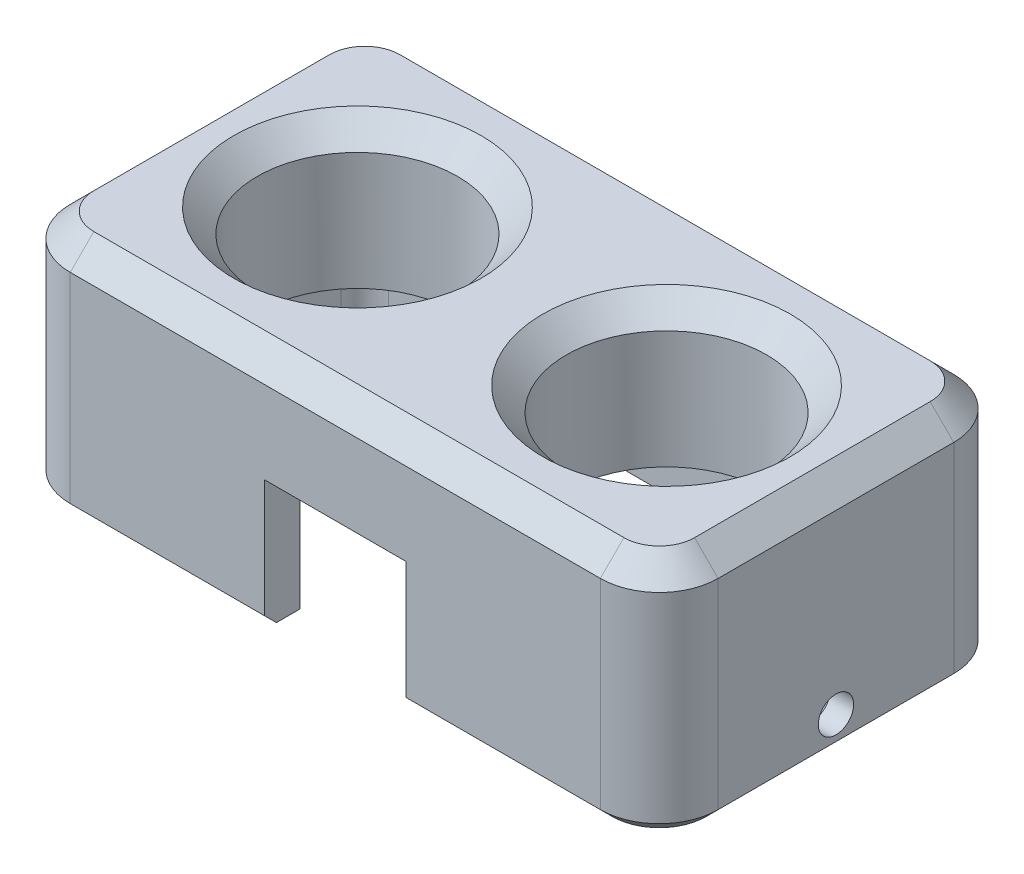
SolidWorks part; units mm, degrees
ref_plane "Front Plane" through (0, 0, 0) normal (0, 0, 1) x (1, 0, 0)
ref_plane "Top Plane" through (0, 0, 0) normal (0, 1, 0) x (1, 0, 0)
ref_plane "Right Plane" through (0, 0, 0) normal (1, 0, 0) x (0, 0, -1)
sketch "Sketch1" plane through (0, 0, 0) normal (0, 1, 0) x (1, 0, 0)
  line L1 (-27.5, -15) -> (27.5, -15)
  line L2 (-27.5, -15) -> (-27.5, 15)
  line L3 (-27.5, 15) -> (27.5, 15)
  line L4 (27.5, -15) -> (27.5, 15)
  line L5 (-27.5, -15) -> (27.5, 15) construction
  line L6 (-27.5, 15) -> (27.5, -15) construction
  point P0 (0, 0)
  dimension "D1" = 30
  dimension "D2" = 55
extrude "Boss-Extrude1" add sketch "Sketch1" along normal blind 12
sketch "Sketch2" plane through (0, 12, 0) normal (0, 1, 0) x (1, 0, 0)
  line L0 (0, 3.5755) -> (0, -2.1377) construction
  line L1 (0, 0) -> (-13.12, 0) construction
  circle A0 centre (-13.12, 0) radius 8.5
  circle A1 centre (13.12, 0) radius 8.5
  circle A2 centre (-13.12, 0) radius 10.5
  circle A3 centre (13.12, 0) radius 10.5
  dimension "D1" = 17
  dimension "D3" = 2
  dimension "D2" = 26.24
extrude "Cut-Extrude1" cut sketch "Sketch2" against normal through all contours A0 | A1 region at (-13.12, 12, 0) region at (13.12, 12, 0)
sketch "Sketch4" plane through (0, 0, 0) normal (0, -1, 0) x (1, 0, 0)
  line L0 (0, -15) -> (0, -7.5) construction
  line L2 (27.5, -15) -> (-27.5, -15) construction
  line L3 (6, -10) -> (-6, -10)
  line L4 (6, -10) -> (6, -5)
  line L5 (6, -5) -> (-6, -5)
  line L6 (-6, -10) -> (-6, -5)
  line L7 (6, -10) -> (-6, -5) construction
  line L8 (6, -5) -> (-6, -10) construction
  dimension "D1" = 12
  dimension "D2" = 5
  dimension "D3" = 5
extrude "Cut-Extrude2" [suppressed] cut sketch "Sketch4" against normal blind 5
fillet "Fillet1" [suppressed] radius 2
sketch "Sketch5" plane through (0, 0, 0) normal (0, -1, 0) x (1, 0, 0)
  line L0 (-27.5, 15) -> (27.5, 15) construction
  line L1 (-6, 6) -> (6, 6)
  line L2 (-6, 6) -> (-6, 15)
  line L3 (-6, 15) -> (6, 15)
  line L4 (6, 6) -> (6, 15)
  line L5 (-6, 6) -> (6, 15) construction
  line L6 (-6, 15) -> (6, 6) construction
  line L7 (0, 10.5) -> (0, 15) construction
  point P0 (0, 10.5)
  dimension "D1" = 12
  dimension "D2" = 9
extrude "Cut-Extrude3" cut sketch "Sketch5" against normal blind 3
fillet "Fillet2" radius 5 4 edges at (27.5, 6, 15) (-27.5, 6, -15) (27.5, 6, -15) (-27.5, 6, 15)
sketch "Sketch6" plane through (0, 0, 0) normal (0, -1, 0) x (1, 0, 0)
  line L8 (24.5, -10) -> (24.5, 10)
  line L9 (22.5, 12) -> (9, 12)
  line L13 (-9, 12) -> (-22.5, 12)
  line L14 (-24.5, 10) -> (-24.5, -10)
  line L15 (-22.5, -12) -> (22.5, -12)
  line L16 (27.5, -10) -> (27.5, 10)
  line L17 (22.5, 15) -> (6, 15)
  line L18 (6, 15) -> (6, 6)
  line L19 (6, 6) -> (-6, 6)
  line L20 (-6, 6) -> (-6, 15)
  line L21 (-6, 15) -> (-22.5, 15)
  line L22 (-27.5, 10) -> (-27.5, -10)
  line L23 (-22.5, -15) -> (22.5, -15)
  line L24 (27.5, -10) -> (27.5, 10)
  line L25 (22.5, 15) -> (6, 15)
  line L26 (6, 15) -> (6, 6)
  line L27 (6, 6) -> (-6, 6)
  line L28 (-6, 6) -> (-6, 15)
  line L29 (-6, 15) -> (-22.5, 15)
  line L30 (-27.5, 10) -> (-27.5, -10)
  line L31 (-22.5, -15) -> (22.5, -15)
  line L32 (-9, 3) -> (-9, 12) construction
  line L33 (9, 3) -> (-9, 3) construction
  line L34 (9, 12) -> (9, 3) construction
  line L35 (-9, 12) -> (-6, 12)
  line L36 (0, 16.6951) -> (0, 15.068) construction
  line L37 (9, 12) -> (6, 12)
  arc A4 (24.5, 10) -> (22.5, 12) centre (22.5, 10) ccw
  arc A5 (-22.5, 12) -> (-24.5, 10) centre (-22.5, 10) ccw
  arc A6 (-24.5, -10) -> (-22.5, -12) centre (-22.5, -10) ccw
  arc A7 (22.5, -12) -> (24.5, -10) centre (22.5, -10) ccw
  arc A8 (27.5, 10) -> (22.5, 15) centre (22.5, 10) ccw
  arc A9 (-22.5, 15) -> (-27.5, 10) centre (-22.5, 10) ccw
  arc A10 (-27.5, -10) -> (-22.5, -15) centre (-22.5, -10) ccw
  arc A11 (22.5, -15) -> (27.5, -10) centre (22.5, -10) ccw
  arc A12 (27.5, 10) -> (22.5, 15) centre (22.5, 10) ccw
  arc A13 (-22.5, 15) -> (-27.5, 10) centre (-22.5, 10) ccw
  arc A14 (-27.5, -10) -> (-22.5, -15) centre (-22.5, -10) ccw
  arc A15 (22.5, -15) -> (27.5, -10) centre (22.5, -10) ccw
  line M15 (27.5, -10) -> (27.5, 10)
  arc M16 (27.5, 10) -> (22.5, 15) centre (22.5, 10) ccw
  line M17 (22.5, 15) -> (6, 15)
  line M18 (6, 15) -> (6, 6)
  line M21 (-6, 15) -> (-22.5, 15)
  arc M22 (-22.5, 15) -> (-27.5, 10) centre (-22.5, 10) ccw
  line M23 (-27.5, 10) -> (-27.5, -10)
  arc M24 (-27.5, -10) -> (-22.5, -15) centre (-22.5, -10) ccw
  line M25 (-22.5, -15) -> (22.5, -15)
  arc M26 (22.5, -15) -> (27.5, -10) centre (22.5, -10) ccw
  dimension "D1" = 0
  dimension "D2" = 3
extrude "Boss-Extrude3" add sketch "Sketch6" along normal blind 8 contours A7 L15 A6 L14 A5 L13 L35 L28 L37 L9 A4 L8 M21 M22 M23 M24 M25 M26 M15 M16 M17 M18 region at (25.1265, 0, 0)
hole_wizard "Ø3.0mm Dowel Hole1" positions "Sketch7" profile "Sketch9" hole size "Ø3.0" standard "ANSI Metric" end condition through all
sketch "Sketch7" plane through (-27.5, 0, 0) normal (-1, 0, 0) x (0, 0, 1)
  line L0 (0, -8) -> (0, -5) construction
  line L2 (10, -8) -> (-10, -8) construction
  point P2 (0, -5)
  dimension "D1" = 3
sketch "Sketch9" plane through (-27.5, -5, 0) normal (0, 1, 0) x (0, 0, 1)
  line L0 (0, 0) -> (0, 55)
  line L1 (0, 55) -> (1.5, 55)
  line L2 (1.5, 55) -> (1.5, 0)
  line L5 (1.5, 0) -> (0, 0)
  line L11 (0, -6.35) -> (0, 107.95) construction
  dimension "Thru Hole Dia." = 3
  dimension "Thru Hole Depth" = 55
sketch "Sketch10" plane through (24.5, 0, 0) normal (-1, 0, 0) x (0, 0, 1)
  line L0 (-10, 0) -> (10, 0) construction
  line L1 (2.8868, -5) -> (1.4434, -2.5)
  line L2 (1.4434, -2.5) -> (-1.4434, -2.5)
  line L3 (-1.4434, -2.5) -> (-2.8868, -5)
  line L4 (-2.8868, -5) -> (-1.4434, -7.5)
  line L5 (-1.4434, -7.5) -> (1.4434, -7.5)
  line L6 (1.4434, -7.5) -> (2.8868, -5)
  line L7 (4, -8) -> (-4, -8)
  line L8 (4, -8) -> (4, 0)
  line L9 (4, 0) -> (-4, 0)
  line L10 (-4, -8) -> (-4, 0)
  line L11 (4, -8) -> (-4, 0) construction
  line L12 (4, 0) -> (-4, -8) construction
  line L13 (-10, -8) -> (10, -8) construction
  line L14 (0, -4) -> (0, -5) construction
  circle A0 centre (0, -5) radius 2.5 construction
  point P1 (0, -4)
  dimension "D1" = 5
  dimension "D2" = 8
extrude "Boss-Extrude4" add sketch "Sketch10" along normal blind 1
mirror "Mirror1" about plane through (0, 0, 0) normal (1, 0, 0) of "Boss-Extrude4"
hole_wizard "Tap Drill for M2x0.4 Tap1" positions "Sketch11" profile "Sketch12" hole size "M2x0.4" standard "ANSI Metric"
sketch "Sketch11" plane through (0, 0, 0) normal (0, -1, 0) x (-1, 0, 0)
  line L1 (-21.15, 8.5) -> (21.15, 8.5)
  line L2 (-21.15, 8.5) -> (-21.15, -8.5)
  line L3 (-21.15, -8.5) -> (21.15, -8.5)
  line L4 (21.15, 8.5) -> (21.15, -8.5)
  line L5 (-21.15, 8.5) -> (21.15, -8.5) construction
  line L6 (-21.15, -8.5) -> (21.15, 8.5) construction
  point P0 (-21.15, 8.5)
  point P3 (21.15, 8.5)
  point P6 (21.15, -8.5)
  point P9 (-21.15, -8.5)
  point P56 (0, 0)
  point P57 (0, 0)
  point P59 (0, 0)
  point P60 (0, 0)
  point P61 (0, 0)
  point P62 (0, 0)
  point P63 (21.425, 8.7)
  point P64 (-21.425, 8.7)
  point P65 (-21.425, -8.7)
  dimension "D1" = 42.3
  dimension "D2" = 17
sketch "Sketch12" plane through (21.15, 0, -8.5) normal (1, 0, 0) x (0, 0, -1)
  line L0 (0, 0) -> (0, 5.4807)
  line L1 (0, 5.4807) -> (0.8, 5)
  line L2 (0.8, 5) -> (0.8, 0)
  line L5 (0.8, 0) -> (0, 0)
  line L10 (0, 5.4807) -> (-0.8, 5) construction
  line L11 (0, -6.35) -> (0, 107.95) construction
  dimension "Hole Dia." = 1.6
  dimension "Hole Depth" = 5
  dimension "Drill Angle" = 118
sketch "Sketch13" plane through (23.5, 0, 0) normal (-1, 0, 0) x (0, 0, 1)
  line L1 (2.8868, -5) -> (1.4434, -2.5)
  line L2 (1.4434, -2.5) -> (-1.4434, -2.5)
  line L3 (-1.4434, -2.5) -> (-2.8868, -5)
  line L4 (-2.8868, -5) -> (-1.4434, -7.5)
  line L5 (-1.4434, -7.5) -> (1.4434, -7.5)
  line L6 (1.4434, -7.5) -> (2.8868, -5)
  circle A0 centre (0, -5) radius 2.5 construction
extrude "Cut-Extrude4" cut sketch "Sketch13" against normal blind 2
mirror "Mirror2" about plane through (0, 0, 0) normal (1, 0, 0) of "Cut-Extrude4"
chamfer "Chamfer1" distance 2 angle 45 10 edges at (-13.12, 12, 8.5) (13.12, 12, 8.5) (-26.0355, 12, 13.5355) (-27.5, 12, 0) (-26.0355, 12, -13.5355) (0, 12, -15) (26.0355, 12, -13.5355) (27.5, 12, 0) (26.0355, 12, 13.5355) (0, 12, 15)
chamfer "Chamfer2" distance 1 angle 45 2 edges at (-26.0355, -8, 13.5355) (-14.25, -8, 15)
